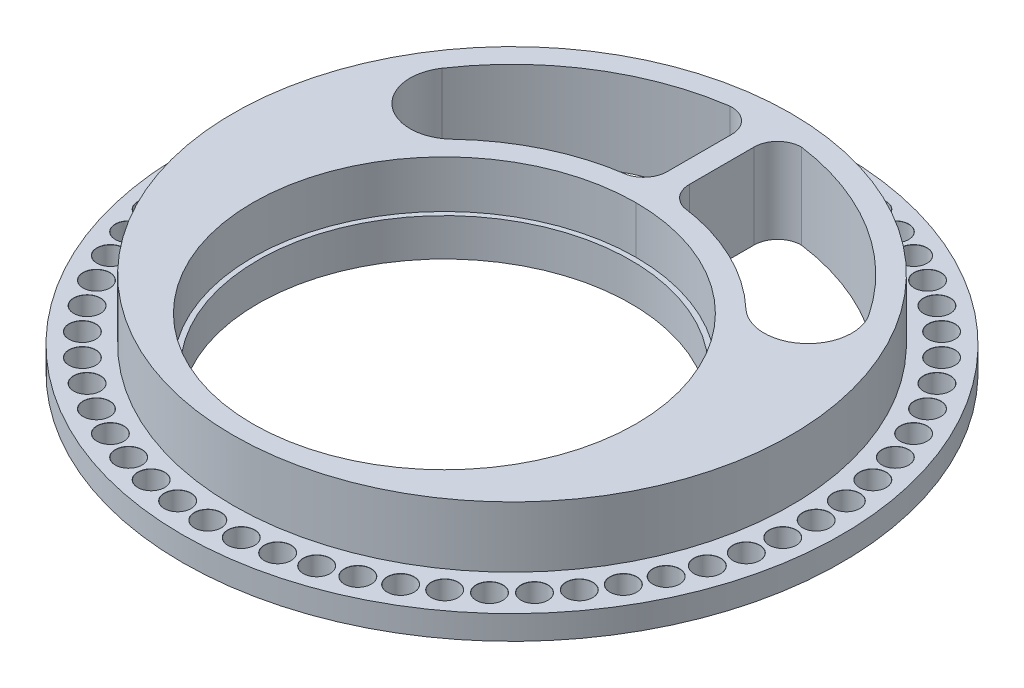
SolidWorks part; units mm, degrees
material "7075-T6, Plate (SS)"
ref_plane "X-Y Datum" through (0, 0, 0) normal (0, 0, 1) x (1, 0, 0)
ref_plane "X-Z Datum" through (0, 0, 0) normal (0, 1, 0) x (1, 0, 0)
ref_plane "Y-Z Datum" through (0, 0, 0) normal (1, 0, 0) x (0, 0, -1)
sketch "Sketch1" plane through (0, 0, 0) normal (0, 1, 0) x (1, 0, 0)
  line L0 (0, 0) -> (0, -12.7) construction
  line L1 (0, -43.0151) -> (0, 43.0151) construction
  line L2 (0, 61.9125) -> (0, 52.3875)
  circle A0 centre (0, -12.7) radius 35.052
  circle A1 centre (0, 0) radius 52.3875 construction
  circle A2 centre (0, 0) radius 57.15 construction
  circle A3 centre (0, 0) radius 61.9125
  point P12 (0, 57.15)
  dimension "D2" = 70.104
  dimension "D3" = 104.775
  dimension "D4" = 123.825
  dimension "D5" = 114.3
  dimension "D1" = 12.7
extrude "Boss-Extrude1" add sketch "Sketch1" along normal blind 4.5212 contours A3 A0 region at (-42.5405, 0, 42.5405)
sketch "Sketch3" plane through (0, 4.5212, 0) normal (0, 1, 0) x (1, 0, 0)
  circle A0 centre (0, 0) radius 52.3875 construction
  circle A1 centre (0, 0) radius 52.3875
extrude "Boss-Extrude2" add sketch "Sketch3" along normal blind 11.43
sketch "Sketch4" plane through (0, 0, 0) normal (0, -1, 0) x (1, 0, 0)
  circle A0 centre (0, 12.7) radius 35.052 construction
  circle A1 centre (0, 12.7) radius 35.052
extrude "Cut-Extrude1" cut sketch "Sketch4" against normal through all
sketch "Sketch9" plane through (0, 15.9512, 0) normal (0, 1, 0) x (1, 0, 0)
  circle A0 centre (0, -12.7) radius 35.052 construction
  circle A1 centre (0, -12.7) radius 35.052 construction
  circle A2 centre (0, -12.7) radius 36
  dimension "D1" = 72
extrude "Cut-Extrude3" cut sketch "Sketch9" against normal blind 8.89
hole_wizard "Ø5.0mm Dowel Hole1" positions "Sketch7" profile "Sketch8" hole size "Ø5.0" standard "ANSI Metric" end condition through all
sketch "Sketch7" plane through (0, 4.5212, 0) normal (0, 1, 0) x (1, 0, 0)
  point P0 (0, 57.15)
sketch "Sketch8" plane through (0, 4.5212, -57.15) normal (1, 0, 0) x (0, 0, 1)
  line L0 (0, 0) -> (0, 4.5212)
  line L1 (0, 4.5212) -> (2.5, 4.5212)
  line L2 (2.5, 4.5212) -> (2.5, 0.025)
  line L3 (2.5, 0.025) -> (2.525, 0)
  line L5 (2.525, 0) -> (0, 0)
  line L6 (-2.5, 0.025) -> (-2.525, 0) construction
  line L11 (0, -6.35) -> (0, 107.95) construction
  dimension "Thru Hole Dia." = 5
  dimension "Thru Hole Depth" = 4.5212
  dimension "Near C'Sink Dia." = 5.05
  dimension "Near C'Sink Angle" = 90
pattern_circular "CirPattern1" count 60 over 360 about axis through (0, 15.9512, 0) along (0, -1, 0) of "Ø5.0mm Dowel Hole1" reverse direction yes
ref_point "Point1"
ref_plane "Plane1" through (0, 0, 0) normal (1, 0, 0) x (0, 0, -1)
split line "Split Line1"
ref_plane "Plane2" through (0, 7.9756, 0) normal (0, 1, 0) x (1, 0, 0)
sketch "Sketch14" plane through (0, 7.9756, 0) normal (0, 1, 0) x (1, 0, 0)
  circle A0 centre (-33.2491, 22.3603) radius 8.255
ref_point "Point4"
sketch "Sketch10" plane through (0, 15.9512, 0) normal (0, 1, 0) x (1, 0, 0)
  circle A0 centre (0, 0) radius 52.3875 construction
  circle A1 centre (0, 0) radius 52.3875 construction
  circle A3 centre (-33.2491, 22.3603) radius 8.255 construction
  circle A4 centre (33.2491, 22.3603) radius 8.255 construction
  arc A7 (0, -52.764) -> (0, 27.364) centre (0, -12.7) ccw
  arc A8 (0, 27.364) -> (0, -52.764) centre (0, -12.7) ccw
  arc A9 (0, -52.764) -> (0, 27.364) centre (0, -12.7) ccw construction
  arc A10 (0, 27.364) -> (0, -52.764) centre (0, -12.7) ccw construction
  circle A29 centre (0, 0) radius 48.3235 construction
  arc A30 (-27.5687, 16.3704) -> (27.5687, 16.3704) centre (0, -12.7) cw
  arc A31 (-40.0992, 26.967) -> (40.0992, 26.967) centre (0, 0) cw
  arc A32 (-40.0992, 26.967) -> (-27.5687, 16.3704) centre (-33.2491, 22.3603) ccw
  arc A33 (27.5687, 16.3704) -> (40.0992, 26.967) centre (33.2491, 22.3603) ccw
  dimension "D3" = 16.51
  dimension "D1" = 4.064
  dimension "D2" = 4.064
extrude "Cut-Extrude5" cut sketch "Sketch10" against normal through all contours A33 A31 A32 A30
sketch "Sketch15" plane through (0, 7.9756, 0) normal (0, 1, 0) x (1, 0, 0)
  line L1 (-2.1171, 31.2835) -> (-2.1171, 43.3958)
  line L4 (2.032, 31.291) -> (2.032, 43.4389)
  line L6 (-2.1764, 48.3235) -> (-2.1667, 48.2749) construction
  line L8 (2.1667, 48.2749) -> (2.1764, 48.3235) construction
  arc A0 (27.5687, 16.3704) -> (-27.5687, 16.3704) centre (0, -12.7) ccw construction
  arc A1 (27.5687, 16.3704) -> (-27.5687, 16.3704) centre (0, -12.7) ccw construction
  arc A2 (40.0992, 26.967) -> (-40.0992, 26.967) centre (0, 0) ccw construction
  arc A3 (-2.1171, 43.3958) -> (-6.9062, 47.8275) centre (-6.5621, 43.3958) ccw
  arc A4 (40.0992, 26.967) -> (-40.0992, 26.967) centre (0, 0) ccw construction
  arc A5 (6.5037, 47.8838) -> (2.032, 43.4389) centre (6.477, 43.4389) ccw
  arc A7 (-2.1171, 31.2835) -> (-5.362, 27.0036) centre (-6.5621, 31.2835) cw
  arc A9 (2.032, 31.291) -> (5.2509, 27.0184) centre (6.477, 31.291) ccw
  arc A10 (-6.9062, 47.8275) -> (6.5037, 47.8838) centre (0, 0) cw
  arc A11 (-5.362, 27.0036) -> (5.2509, 27.0184) centre (0, -12.7) cw
  point P9 (0, 37.4715)
  dimension "D1" = 4.445
  dimension "D2" = 2.1171
  dimension "D3" = 4.445
  dimension "D4" = 2.032
  dimension "D5" = 43.4389
  dimension "D6" = 31.2835
  dimension "D7" = 2.1171
  dimension "D8" = 12.148
  dimension "D9" = 12.1123
extrude "Boss-Extrude3" add sketch "Sketch15" along normal up to surface and the other way up to surface contours A9 L4 A5 A10 A3 L1 A7 A11 region at (-0.0494, 7.9756, -38.2136) up to face at (0, 15.9512, -26.9504) other way up to face at (0, 0, -26.9504)
sketch "Sketch20" plane through (0, 4.5212, 0) normal (0, 1, 0) x (1, 0, 0)
  circle A0 centre (0, 0) radius 52.3875
  circle A2 centre (0, 0) radius 66.6087
sketch "Sketch25" plane through (0, 15.9512, 0) normal (0, 1, 0) x (1, 0, 0)
  line L6 (-4.6571, 31.2835) -> (-4.6571, 43.3958)
  line L7 (-4.6571, 31.2835) -> (-4.6571, 43.3958)
  line L12 (4.572, 43.4389) -> (4.572, 31.291)
  line L13 (4.572, 43.4389) -> (4.572, 31.291)
  circle A1 centre (-51.685, -7.6867) radius 0.134
  circle A2 centre (49.3335, -18.9489) radius 0.46
  arc A3 (48.8818, -18.8622) -> (48.9404, -18.71) centre (-0.2183, 0.1504) ccw
  arc A4 (48.8818, -18.8622) -> (48.9404, -18.71) centre (-0.2183, 0.1504) ccw
  arc A45 (-4.6571, 43.3958) -> (-6.6423, 45.2991) centre (-6.5621, 43.3958) ccw
  arc A46 (-5.9167, 29.4912) -> (-4.6571, 31.2835) centre (-6.5621, 31.2835) ccw
  arc A47 (-5.9167, 29.4912) -> (-29.3165, 18.2135) centre (0, -12.7) ccw
  arc A48 (-37.9914, 25.5495) -> (-29.3165, 18.2135) centre (-33.2491, 22.3603) ccw
  arc A49 (-6.6423, 45.2991) -> (-37.9914, 25.5495) centre (0, 0) ccw
  arc A50 (-4.6571, 43.3958) -> (-6.6423, 45.2991) centre (-6.5621, 43.3958) ccw
  arc A51 (-5.9167, 29.4912) -> (-4.6571, 31.2835) centre (-6.5621, 31.2835) ccw
  arc A52 (-5.9167, 29.4912) -> (-29.3165, 18.2135) centre (0, -12.7) ccw
  arc A53 (-37.9914, 25.5495) -> (-29.3165, 18.2135) centre (-33.2491, 22.3603) ccw
  arc A54 (-6.6423, 45.2991) -> (-37.9914, 25.5495) centre (0, 0) ccw
  circle A68 centre (-0.2183, 0.1504) radius 52.1224
  circle A69 centre (0, -12.7) radius 32.512
  circle A70 centre (0, -12.7) radius 32.512
  arc A72 (29.3165, 18.2135) -> (37.9914, 25.5495) centre (33.2491, 22.3603) ccw
  arc A73 (4.572, 31.291) -> (5.8124, 29.5056) centre (6.477, 31.291) ccw
  arc A74 (29.3165, 18.2135) -> (5.8124, 29.5056) centre (0, -12.7) ccw
  arc A75 (37.9914, 25.5495) -> (6.3564, 45.3401) centre (0, 0) ccw
  arc A76 (6.3564, 45.3401) -> (4.572, 43.4389) centre (6.477, 43.4389) ccw
  arc A77 (29.3165, 18.2135) -> (37.9914, 25.5495) centre (33.2491, 22.3603) ccw
  arc A78 (4.572, 31.291) -> (5.8124, 29.5056) centre (6.477, 31.291) ccw
  arc A79 (29.3165, 18.2135) -> (5.8124, 29.5056) centre (0, -12.7) ccw
  arc A80 (37.9914, 25.5495) -> (6.3564, 45.3401) centre (0, 0) ccw
  arc A81 (6.3564, 45.3401) -> (4.572, 43.4389) centre (6.477, 43.4389) ccw
  arc M3 (27.5687, 16.3704) -> (5.2509, 27.0184) centre (0, -12.7) ccw
  arc M4 (5.2509, 27.0184) -> (2.032, 31.291) centre (6.477, 31.291) cw
  line M5 (2.032, 31.291) -> (2.032, 43.4389)
  arc M6 (2.032, 43.4389) -> (6.5037, 47.8838) centre (6.477, 43.4389) cw
  arc M7 (6.5037, 47.8838) -> (40.0992, 26.967) centre (0, 0) cw
  arc M8 (40.0992, 26.967) -> (27.5687, 16.3704) centre (33.2491, 22.3603) cw
  arc M9 (-5.362, 27.0036) -> (-27.5687, 16.3704) centre (0, -12.7) ccw
  arc M10 (-27.5687, 16.3704) -> (-40.0992, 26.967) centre (-33.2491, 22.3603) cw
  arc M11 (-40.0992, 26.967) -> (-6.9062, 47.8275) centre (0, 0) cw
  arc M12 (-6.9062, 47.8275) -> (-2.1171, 43.3958) centre (-6.5621, 43.3958) cw
  line M13 (-2.1171, 43.3958) -> (-2.1171, 31.2835)
  arc M14 (-2.1171, 31.2835) -> (-5.362, 27.0036) centre (-6.5621, 31.2835) cw
  arc M15 (0, 23.3) -> (0, -48.7) centre (0, -12.7) cw
  arc M16 (0, -48.7) -> (0, 23.3) centre (0, -12.7) cw
  dimension "D1" = 2.54
  dimension "D2" = 2.54
  dimension "D3" = 2.54
extrude "Boss-Extrude5" [suppressed] add sketch "Sketch25" along normal blind 1.27 contours A54 A50 L7 A51 A52 A53 M9 M14 M13 M12 M11 M10 | A70 M15 M16 | A68 A1 M16 M15 M14 M9 M10 M11 M12 M13 M8 M3 M4 M5 M6 M7 | A81 A80 A77 A79 A78 L13 M3 M8 M7 M6 M5 M4
sketch "Sketch26" plane through (0, 0, 0) normal (0, -1, 0) x (-1, 0, 0)
  point P0 (-19.9732, 32.7446)
  point P1 (21.7792, 32.7446)
  point P2 (0, -12.7)
  point P3 (23.1486, 31.5183)
  point P5 (21.7792, 32.7446)
sketch "Sketch27" plane through (0, 0, 0) normal (0, -1, 0) x (1, 0, 0)
  circle A0 centre (0, 12.7) radius 9.525
  circle A1 centre (0, 12.7) radius 20.32 construction
  circle A2 centre (-20.32, 12.7) radius 3.2639
  circle A3 centre (20.32, 12.7) radius 3.2639
  circle A4 centre (19.9732, -32.7446) radius 3.2639
  circle A5 centre (-21.7792, -32.7446) radius 3.2639
  point P12 (0, 0)
  point P14 (0, 0)
  dimension "D1" = 19.05
  dimension "D2" = 40.64
  dimension "D3" = 6.5278
